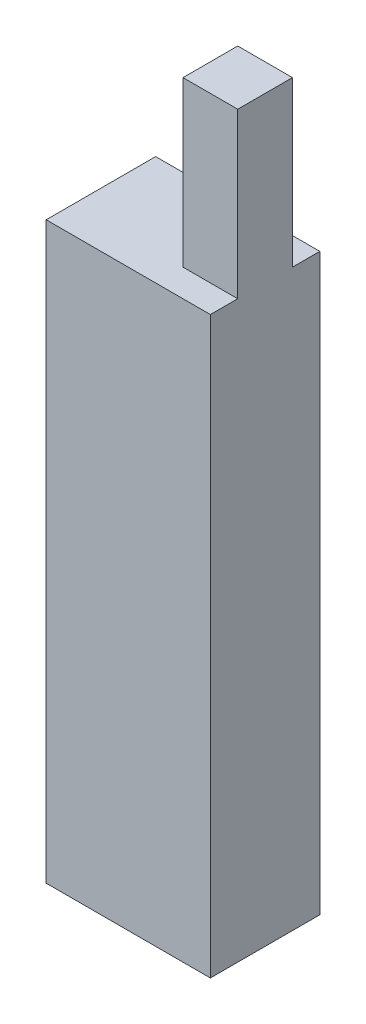
SolidWorks part; units mm, degrees
ref_plane "Front Plane" through (0, 0, 0) normal (0, 0, 1) x (1, 0, 0)
ref_plane "Top Plane" through (0, 0, 0) normal (0, 1, 0) x (1, 0, 0)
ref_plane "Right Plane" through (0, 0, 0) normal (1, 0, 0) x (0, 0, -1)
sketch "Sketch3" plane through (0, 0, 0) normal (0, 0, 1) x (1, 0, 0)
  line L0 (0, 0) -> (0, -5)
  line L1 (0, -5) -> (20, -5)
  line L2 (20, -5) -> (20, -25)
  line L3 (0, 0) -> (20, 0)
  line L4 (20, 0) -> (20, 30)
  line L5 (20, 30) -> (30, 30)
  line L6 (30, 30) -> (30, -25)
  line L7 (30, -25) -> (20, -25)
  dimension "D1" = 20
  dimension "D2" = 20
  dimension "D3" = 20
  dimension "D4" = 5
  dimension "D5" = 10
  dimension "D6" = 55
extrude "Boss-Extrude3" add sketch "Sketch3" along normal blind 10
sketch "Sketch5" plane through (0, 0, 10) normal (0, 0, 1) x (1, 0, 0)
  line L5 (0, 0) -> (30, 0)
  line L6 (0, 0) -> (0, -25)
  line L7 (0, -25) -> (30, -25)
  line L8 (30, 0) -> (30, -25)
extrude "Boss-Extrude5" add sketch "Sketch5" along normal blind 5
sketch "Sketch7" plane through (0, 0, 0) normal (0, 0, -1) x (-1, 0, 0)
  line L0 (-20, 0) -> (-30, 0)
  line L1 (-30, 0) -> (-30, -25)
  line L2 (-30, -25) -> (-20, -25)
  line L3 (-20, -25) -> (-20, -5)
  line L4 (-20, -5) -> (0, -5)
  line L5 (0, -5) -> (0, 0)
  line L6 (0, 0) -> (-20.7589, 0)
  line M8 (0, 0) -> (-20, 0)
  line M11 (-30, 30) -> (-30, -25)
  line M12 (-30, -25) -> (-20, -25)
  line M13 (-20, -25) -> (-20, -5)
  line M14 (-20, -5) -> (0, -5)
  line M15 (0, -5) -> (0, 0)
extrude "Boss-Extrude7" add sketch "Sketch7" along normal blind 5 contours L0 M8 M11 M12 M13 M14 M15 region at (20.7143, -9.6429, 0)
sketch "Sketch10" plane through (0, -25, 0) normal (0, -1, 0) x (1, 0, 0)
  line L0 (0, 10) -> (20, 10)
  line L1 (20, 10) -> (20, -5)
  line L2 (30, -5) -> (20, -5) construction
  line L3 (20, -5) -> (30, -5)
  line L4 (30, -5) -> (30, 15)
  line L5 (30, 15) -> (0, 15)
  line L6 (0, 15) -> (0, 10)
extrude "Boss-Extrude8" add sketch "Sketch10" along normal up to surface (80 mm away)
